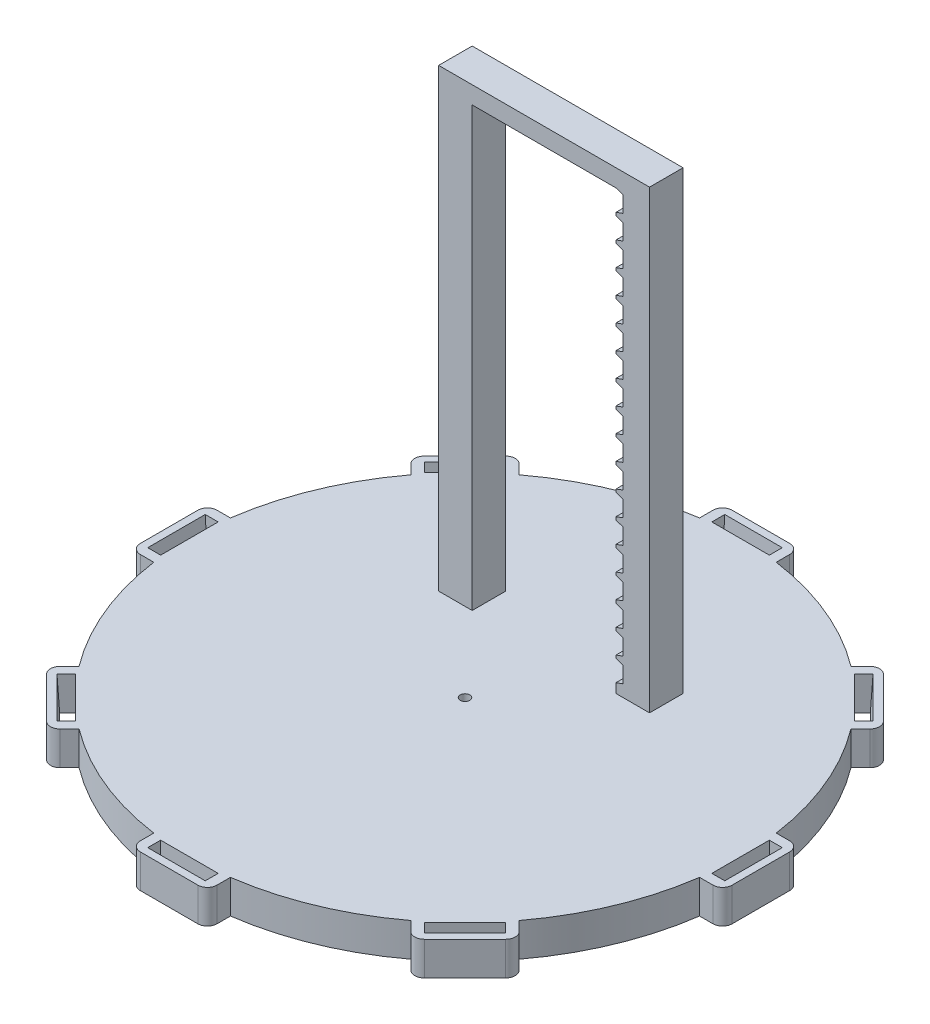
SolidWorks part; units mm, degrees
ref_plane "Front Plane" through (0, 0, 0) normal (0, 0, 1) x (1, 0, 0)
ref_plane "Top Plane" through (0, 0, 0) normal (0, 1, 0) x (1, 0, 0)
ref_plane "Right Plane" through (0, 0, 0) normal (1, 0, 0) x (0, 0, -1)
sketch "Sketch1" plane through (0, 0, 0) normal (0, 1, 0) x (1, 0, 0)
  line L0 (-8, 56.9408) -> (-8, 59.7408)
  line L1 (0, 57.5) -> (0, -57.5) construction
  line L2 (8, 56.9408) -> (8, 59.7408)
  line L3 (-6, 61.7408) -> (6, 61.7408)
  line L4 (39.4147, 47.8999) -> (47.8999, 39.4147)
  line L9 (34.6063, 45.9201) -> (36.5862, 47.8999)
  line L10 (45.9201, 34.6063) -> (47.8999, 36.5862)
  line L15 (61.7408, 6) -> (61.7408, -6)
  line L16 (56.9408, 8) -> (59.7408, 8)
  line L17 (56.9408, -8) -> (59.7408, -8)
  line L22 (47.8999, -39.4147) -> (39.4147, -47.8999)
  line L23 (45.9201, -34.6063) -> (47.8999, -36.5862)
  line L24 (34.6063, -45.9201) -> (36.5862, -47.8999)
  line L29 (6, -61.7408) -> (-6, -61.7408)
  line L30 (8, -56.9408) -> (8, -59.7408)
  line L31 (-8, -56.9408) -> (-8, -59.7408)
  line L36 (-39.4147, -47.8999) -> (-47.8999, -39.4147)
  line L37 (-34.6063, -45.9201) -> (-36.5862, -47.8999)
  line L38 (-45.9201, -34.6063) -> (-47.8999, -36.5862)
  line L43 (-61.7408, -6) -> (-61.7408, 6)
  line L44 (-56.9408, -8) -> (-59.7408, -8)
  line L45 (-56.9408, 8) -> (-59.7408, 8)
  line L50 (-47.8999, 39.4147) -> (-39.4147, 47.8999)
  line L51 (-45.9201, 34.6063) -> (-47.8999, 36.5862)
  line L52 (-34.6063, 45.9201) -> (-36.5862, 47.8999)
  arc A0 (-8, 56.9408) -> (-34.6063, 45.9201) centre (0, 0) ccw
  arc A1 (6, 61.7408) -> (8, 59.7408) centre (6, 59.7408) cw
  arc A2 (-6, 61.7408) -> (-8, 59.7408) centre (-6, 59.7408) ccw
  arc A3 (39.4147, 47.8999) -> (36.5862, 47.8999) centre (38.0005, 46.4857) ccw
  arc A4 (47.8999, 39.4147) -> (47.8999, 36.5862) centre (46.4857, 38.0005) cw
  arc A5 (61.7408, 6) -> (59.7408, 8) centre (59.7408, 6) ccw
  arc A6 (61.7408, -6) -> (59.7408, -8) centre (59.7408, -6) cw
  arc A7 (47.8999, -39.4147) -> (47.8999, -36.5862) centre (46.4857, -38.0005) ccw
  arc A8 (39.4147, -47.8999) -> (36.5862, -47.8999) centre (38.0005, -46.4857) cw
  arc A9 (6, -61.7408) -> (8, -59.7408) centre (6, -59.7408) ccw
  arc A10 (-6, -61.7408) -> (-8, -59.7408) centre (-6, -59.7408) cw
  arc A11 (-39.4147, -47.8999) -> (-36.5862, -47.8999) centre (-38.0005, -46.4857) ccw
  arc A12 (-47.8999, -39.4147) -> (-47.8999, -36.5862) centre (-46.4857, -38.0005) cw
  arc A13 (-61.7408, -6) -> (-59.7408, -8) centre (-59.7408, -6) ccw
  arc A14 (-61.7408, 6) -> (-59.7408, 8) centre (-59.7408, 6) cw
  arc A15 (-47.8999, 39.4147) -> (-47.8999, 36.5862) centre (-46.4857, 38.0005) ccw
  arc A16 (-39.4147, 47.8999) -> (-36.5862, 47.8999) centre (-38.0005, 46.4857) cw
  arc A17 (-45.9201, 34.6063) -> (-56.9408, 8) centre (0, 0) ccw
  arc A18 (-56.9408, -8) -> (-45.9201, -34.6063) centre (0, 0) ccw
  arc A19 (34.6063, 45.9201) -> (8, 56.9408) centre (0, 0) ccw
  arc A20 (-34.6063, -45.9201) -> (-8, -56.9408) centre (0, 0) ccw
  arc A21 (8, -56.9408) -> (34.6063, -45.9201) centre (0, 0) ccw
  arc A22 (45.9201, -34.6063) -> (56.9408, -8) centre (0, 0) ccw
  arc A23 (56.9408, 8) -> (45.9201, 34.6063) centre (0, 0) ccw
  point P11 (8, 61.7408)
  point P14 (-8, 61.7408)
  point P17 (-8, 58.3408)
  point P98 (0, 0)
  dimension "D1" = 115
  dimension "D2" = 2
  dimension "D3" = 16
  dimension "D4" = 2.8
  dimension "D7" = 8
extrude "Boss-Extrude1" add sketch "Sketch1" along normal blind 7
sketch "Sketch2" plane through (0, 7, 0) normal (0, 1, 0) x (1, 0, 0)
  line L0 (-57.5, 0) -> (57.5, 0) construction
  line L1 (0, 0) -> (0, 20) construction
  line L7 (15, 16.5) -> (22, 16.5)
  line L14 (0, 20) -> (29.8122, 20) construction
  line L15 (0, 20) -> (-18.5, 20) construction
  line L17 (15, 16.5) -> (15, 23.5)
  line L18 (-22, 23.5) -> (-15, 23.5)
  line L19 (-22, 23.5) -> (-22, 16.5)
  line L20 (-22, 16.5) -> (-15, 16.5)
  line L21 (-15, 23.5) -> (-15, 16.5)
  line L22 (-22, 23.5) -> (-15, 16.5) construction
  line L23 (-22, 16.5) -> (-15, 23.5) construction
  line L24 (15, 23.5) -> (22, 23.5)
  line L25 (22, 16.5) -> (22, 23.5)
  line L26 (15, 16.5) -> (22, 23.5) construction
  line L27 (15, 23.5) -> (22, 16.5) construction
  circle A0 centre (0, 0) radius 57.5 construction
  point P8 (18.5, 20)
  dimension "D1" = 7
  dimension "D2" = 30
  dimension "D3" = 15
  dimension "D4" = 20
  dimension "D5" = 7
extrude "Boss-Extrude2" add sketch "Sketch2" along normal blind 95
sketch "Sketch15" plane through (0, 0, 0) normal (0, -1, 0) x (1, 0, 0)
  circle A0 centre (0, 0) radius 1
  dimension "D1" = 2
extrude "Cut-Extrude3" cut sketch "Sketch15" along direction (0, 1, 0) on the side against the normal up to surface (7 mm away) contours A0 up to face at (0, 7, 0)
sketch "Sketch16" plane through (0, 0, 0) normal (0, -1, 0) x (1, 0, 0)
  line L1 (-6, 59.8) -> (6, 59.8)
  line L2 (-6, 59.8) -> (-6, 57.5)
  line L3 (-6, 57.5) -> (6, 57.5)
  line L4 (6, 59.8) -> (6, 57.5)
  point P5 (0, 57.5)
  dimension "D1" = 2.3
  dimension "D2" = 12
  dimension "D3" = 57.5
sketch "Sketch17" plane through (0, 7, 0) normal (0, 1, 0) x (1, 0, 0)
  line L0 (-6, -57.5) -> (6, -57.5) construction
  line L1 (-6, -57.5) -> (6, -57.5)
  line L2 (-6, -57.5) -> (-6, -60.2)
  line L3 (-6, -60.2) -> (6, -60.2)
  line L4 (6, -60.2) -> (6, -57.5)
  dimension "D1" = 2.7
ref_axis "Axis1" through (0, 107.1, 0) along (0, -1, 0)
loft "Cut-Loft2" cut profiles "Sketch16", "Sketch17"
pattern_circular "CirPattern1" count 8 over 360 about axis through (0, 107.1, 0) along (0, -1, 0) of "Cut-Loft2"
sketch "Sketch19" plane through (0, 0, -23.5) normal (0, 0, -1) x (-1, 0, 0)
  line L0 (-22, 102) -> (-16.5, 102)
  line L1 (-22, 102) -> (-15, 102) construction
  line L2 (-22, 102) -> (-22, 7) construction
  line L3 (-16.5, 102) -> (-16.5, 101.89)
  line L4 (-16.5, 102) -> (-16.5, 100.9)
  line L5 (-16.5, 100.9) -> (-15, 100.354)
  line L6 (-15, 102) -> (-15, 7) construction
  line L7 (-15, 100.354) -> (-15, 98.354)
  line L8 (-15, 98.354) -> (-16.5, 97.8081)
  line L9 (-16.5, 97.8081) -> (-16.5, 96.7081)
  line L10 (-16.5, 102) -> (-16.5, 7) construction
  line L11 (-16.5, 100.9) -> (-16.5, 97.8081)
  line L12 (-15, 91.954) -> (-16.5, 91.4081)
  line L13 (-15, 93.954) -> (-15, 91.954)
  line L14 (-16.5, 94.5) -> (-15, 93.954)
  line L15 (-15, 102) -> (-15, 7)
  line M2 (-15, 7) -> (-15, 102)
  dimension "D1" = 5.5
  dimension "D2" = 1.1
  dimension "D3" = 2
  dimension "D4" = 1.1
  dimension "D5" = 110
  dimension "D6" = 110
  dimension "D7" = 2
extrude "Cut-Extrude5" cut sketch "Sketch19" against normal blind 10 contours L9 L10 L14 L8 M2 region at (15.7146, 96.154, -23.5)
pattern_linear "LPattern1" count 18 spacing 5 along (0, -1, 0) of "Cut-Extrude5"
sketch "Sketch20" plane through (15, 0, 0) normal (-1, 0, 0) x (0, 0, 1)
  line L4 (-23.5, 102) -> (-23.5, 98.354)
  line L5 (-23.5, 98.354) -> (-16.5, 98.354)
  line L6 (-16.5, 98.354) -> (-16.5, 102)
  line L7 (-16.5, 102) -> (-23.5, 102)
  line L8 (-23.5, 102) -> (-23.5, 98.354)
  line L9 (-23.5, 98.354) -> (-16.5, 98.354)
  line L10 (-16.5, 98.354) -> (-16.5, 102)
  line L11 (-16.5, 102) -> (-23.5, 102)
  dimension "D1" = 0
extrude "Boss-Extrude3" add sketch "Sketch20" along normal up to surface (30 mm away) up to face at (-15, 54.5, -20)
equation "\"85.00.00mm\"=8500"
